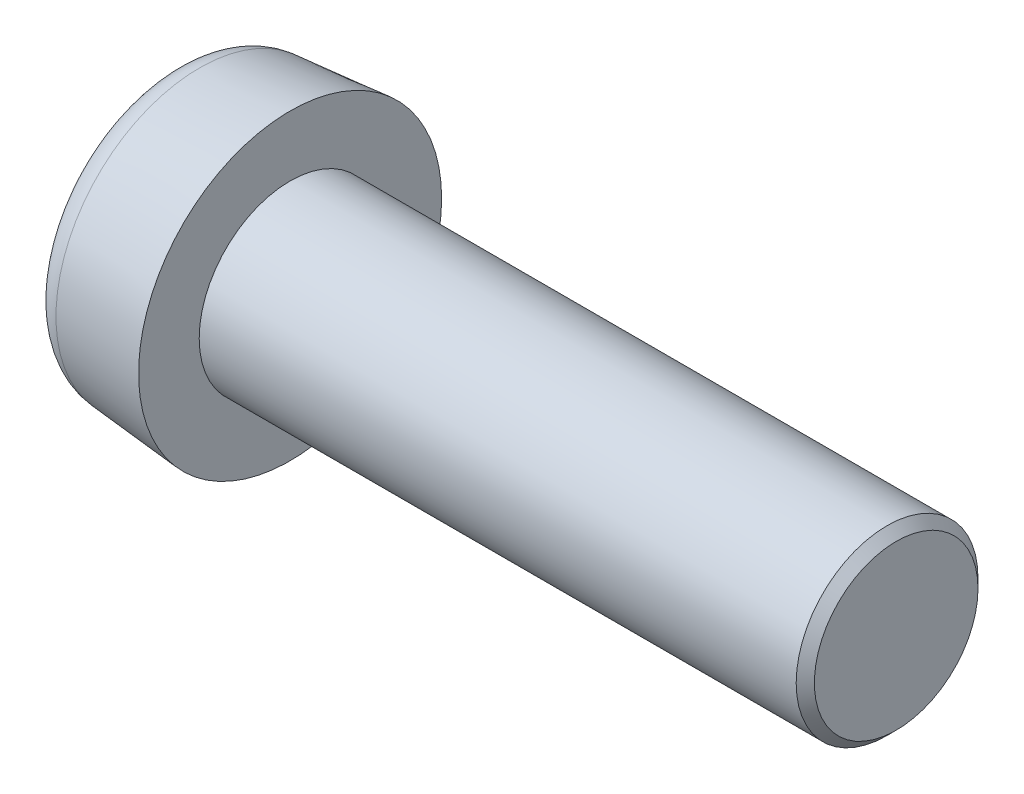
SolidWorks part; units mm, degrees
ref_plane "Front" through (0, 0, 0) normal (0, 0, 1) x (1, 0, 0)
ref_plane "Top" through (0, 0, 0) normal (0, 1, 0) x (1, 0, 0)
ref_plane "Right" through (0, 0, 0) normal (1, 0, 0) x (0, 0, -1)
ref_plane "Plane1" through (3.9, 0, 0) normal (1, 0, 0) x (0, 0, -1)
sketch "Sketch1" plane through (3.9, 0, 0) normal (1, 0, 0) x (0, 0, -1)
  circle A0 centre (0, 0) radius 5
  dimension "dk" = 10
extrude "BaseHead" add sketch "Sketch1" against normal blind 3.9 draft 5
sketch "Sketch2" plane through (3.9, 0, 0) normal (1, 0, 0) x (0, 0, -1)
  circle A0 centre (0, 0) radius 3
extrude "BaseBody" add sketch "Sketch2" along normal blind 20
cosmetic thread "ThreadCosmetic1" parameters "bb"=20, "THD_MINOR"=4.917
fillet "HeadFillet" [suppressed] radius 0.25
sketch "Sketch3" plane through (0, 0, 0) normal (1, 0, 0) x (0, 0, -1)
  line L1 (2.396, 0) -> (1.198, 2.075)
  line L2 (1.198, 2.075) -> (-1.198, 2.075)
  line L3 (-1.198, 2.075) -> (-2.396, 0)
  line L4 (-2.396, 0) -> (-1.198, -2.075)
  line L5 (-1.198, -2.075) -> (1.198, -2.075)
  line L6 (1.198, -2.075) -> (2.396, 0)
  circle A0 centre (0, 0) radius 2.075 construction
  dimension "B" = 4.15
extrude "HexagonSocket" cut sketch "Sketch3" along normal blind 2
sketch "Sketch4" plane through (2, 0, 0) normal (-1, 0, 0) x (0, 0, 1)
  line L0 (1.198, -2.075) -> (-1.198, -2.075) construction
  line L1 (-1.198, -2.075) -> (-2.396, 0) construction
  line L2 (-2.396, 0) -> (-1.198, 2.075) construction
  line L3 (2.396, 0) -> (1.198, -2.075) construction
  line L4 (1.198, 2.075) -> (2.396, 0) construction
  line L5 (-1.198, 2.075) -> (1.198, 2.075) construction
  line L6 (1.198, -2.075) -> (-1.198, -2.075)
  line L7 (-1.198, -2.075) -> (-2.396, 0)
  line L8 (-2.396, 0) -> (-1.198, 2.075)
  line L9 (2.396, 0) -> (1.198, -2.075)
  line L10 (1.198, 2.075) -> (2.396, 0)
  line L11 (-1.198, 2.075) -> (1.198, 2.075)
extrude "Cut-Extrude2" cut sketch "Sketch4" against normal blind 5 draft 60
fillet "TopFillet" radius 1 1 edges at (0, 0, -4.6588)
chamfer "Chamfer1" distance 0.3 angle 45 1 edges at (23.9, 0, -3)
sketch "Sketch5" plane through (0, 0, 0) normal (0, 0, 1) x (1, 0, 0)
  line L0 (23.6, 2.531) -> (23.8708, 3)
  line L1 (23.8708, 3) -> (23.8708, 3.5415)
  line L2 (23.8708, 3.5415) -> (23.3293, 3.5415)
  line L3 (23.3293, 3.5415) -> (23.3293, 3)
  line L4 (23.3293, 3) -> (23.6, 2.531)
  line L5 (0, 0) -> (26.2596, 0) construction
  line L6 (23.6, -3) -> (23.6, 3) construction
  dimension "D1" = 0.5415
  dimension "D2" = 6
revolve "Cut-Revolve10" [suppressed] cut sketch "Sketch5" angle 360 about L5
pattern_linear "LPattern10" [suppressed] count 31 spacing 0.6498 along (-1, 0, 0) of bodies 105
equation "\"D1@Plane1\" = \"K@BaseHead\""
equation "\"D2@Sketch5\" = \"d@Sketch2\""
equation "\"D1@Sketch5\" =  ( \"d@Sketch2\" - \"THD_MINOR@ThreadCosmetic1\" )  / 2"
equation "\"D3@LPattern10\" = \"D1@Sketch5\" * 1.2"
equation "\"D1@LPattern10\" = \"bb@ThreadCosmetic1\" / \"D3@LPattern10\""
